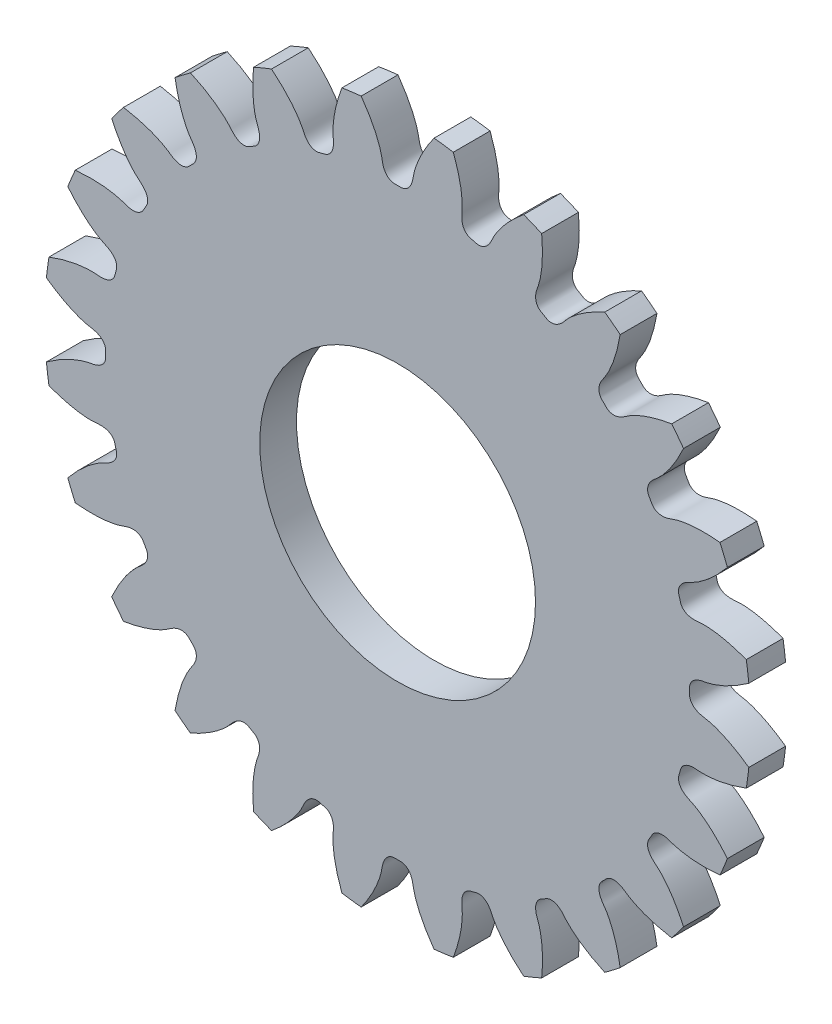
SolidWorks part; units mm, degrees
ref_plane "Alzado" through (0, 0, 0) normal (0, 0, 1) x (1, 0, 0)
ref_plane "Planta" through (0, 0, 0) normal (0, 1, 0) x (1, 0, 0)
ref_plane "Vista lateral" through (0, 0, 0) normal (1, 0, 0) x (0, 0, -1)
ref_axis "Eje1" through (0, 0, 55) along (0, 0, -1)
sketch "SketchRevolveSpur03" plane through (0, 0, 0) normal (1, 0, 0) x (0, 0, -1)
  line L0 (0, 0) -> (1, 0) construction
  line L1 (-0.125, 0) -> (-0.125, 1.9205)
  line L2 (-0.125, 1.9205) -> (0.075, 1.9205)
  line L3 (0.075, 1.9205) -> (0.075, 0)
  line L4 (0.075, 0) -> (-0.125, 0)
  dimension "D1" = 0.2
revolve "Spur03" add sketch "SketchRevolveSpur03" angle 360 about L0
sketch "SketchToothSpur03" plane through (0, 0, 0) normal (0, 0, 1) x (1, 0, 0)
  arc A0 (1.9171, 0.2032) -> (1.9171, -0.2032) centre (0, 0) cw
  spline S0 degree 3 poles (1.9171, -0.2032) (1.9027, -0.1926) (1.8812, -0.1777) (1.8524, -0.1597) (1.8323, -0.1479) (1.8131, -0.1373) (1.7949, -0.128) (1.7777, -0.1198) (1.7615, -0.1126) (1.7465, -0.1065) (1.7325, -0.1013) (1.7198, -0.097) (1.7084, -0.0935) (1.6981, -0.0906) (1.6892, -0.0885) (1.6792, -0.0863) (1.6705, -0.085) (1.6631, -0.0837) (1.6589, -0.0829) (1.6548, -0.082) (1.6507, -0.081) (1.6468, -0.0799) (1.6429, -0.0788) (1.6391, -0.0775) (1.6354, -0.0761) (1.6317, -0.0746) (1.6281, -0.073) (1.6246, -0.0712) (1.6211, -0.0692) (1.6176, -0.0671) (1.6142, -0.0648) (1.6108, -0.0622) (1.6075, -0.0593) (1.6042, -0.056) (1.6011, -0.0524) (1.598, -0.0484) (1.5952, -0.0439) (1.5927, -0.0388) (1.5906, -0.0333) (1.589, -0.0274) (1.5882, -0.0215) (1.5878, -0.0124) (1.5883, 0) (1.5878, 0.0124) (1.5882, 0.0215) (1.589, 0.0274) (1.5906, 0.0333) (1.5927, 0.0388) (1.5952, 0.0439) (1.598, 0.0484) (1.6011, 0.0524) (1.6042, 0.056) (1.6075, 0.0593) (1.6108, 0.0622) (1.6142, 0.0648) (1.6176, 0.0671) (1.6211, 0.0692) (1.6246, 0.0712) (1.6281, 0.073) (1.6317, 0.0746) (1.6354, 0.0761) (1.6391, 0.0775) (1.6429, 0.0788) (1.6468, 0.0799) (1.6507, 0.081) (1.6548, 0.082) (1.6589, 0.0829) (1.6631, 0.0837) (1.6705, 0.085) (1.6792, 0.0863) (1.6892, 0.0885) (1.6981, 0.0906) (1.7084, 0.0935) (1.7198, 0.097) (1.7325, 0.1013) (1.7465, 0.1065) (1.7615, 0.1126) (1.7777, 0.1198) (1.7949, 0.128) (1.8131, 0.1373) (1.8323, 0.1479) (1.8524, 0.1597) (1.8812, 0.1777) (1.9027, 0.1926) (1.9171, 0.2032) knots 0 0 0 0 0.065546 0.095731 0.124192 0.150927 0.175938 0.199224 0.220785 0.240621 0.258732 0.275119 0.28978 0.302717 0.313929 0.323416 0.34044 0.345783 0.351027 0.356179 0.361247 0.366241 0.37117 0.376048 0.380887 0.385705 0.390519 0.395351 0.400226 0.405172 0.410221 0.41541 0.420778 0.426367 0.432221 0.438379 0.444875 0.451724 0.458919 0.466423 0.474165 0.480555 0.5 0.519445 0.525835 0.533577 0.541081 0.548276 0.555125 0.561621 0.567779 0.573633 0.579222 0.58459 0.589779 0.594828 0.599774 0.604649 0.609481 0.614295 0.619113 0.623952 0.62883 0.633759 0.638753 0.643821 0.648973 0.654217 0.65956 0.676584 0.686071 0.697283 0.71022 0.724881 0.741268 0.759379 0.779215 0.800776 0.824062 0.849073 0.875808 0.904269 0.934454 1 1 1 1
extrude "ToothExtrudeCutSpur03" cut sketch "SketchToothSpur03" against normal blind 0.125 and the other way blind 0.125
pattern_circular "PatternSpur03" count 24 every 15 about axis through (0, 0, 55) along (0, 0, -1) of "ToothExtrudeCutSpur03"
sketch "AuxiliarySketchSpur03" plane through (0, 0, 0) normal (0, 0, 1) x (1, 0, 0)
  circle A0 centre (0, 0) radius 1.7727 construction
  circle A1 centre (0, 0) radius 1.6658 construction
  circle A2 centre (0, 0) radius 1.6727 construction
  circle A3 centre (0, 0) radius 1.9205 construction
  circle A4 centre (0, 0) radius 1.5881 construction
  dimension "PitchDiameter" = 3.5455
  dimension "BaseDiameter" = 3.3316
  dimension "FormDiameter" = 3.3454
  dimension "MajorDiameter" = 3.8409
  dimension "MinorDiameter" = 3.1761
sketch "Croquis1" plane through (0, 0, 0.125) normal (0, 0, 1) x (1, 0, 0)
  circle A0 centre (0, 0) radius 0.75
  dimension "D1" = 1.5
extrude "Cortar-Extruir1" cut sketch "Croquis1" against normal up to next
